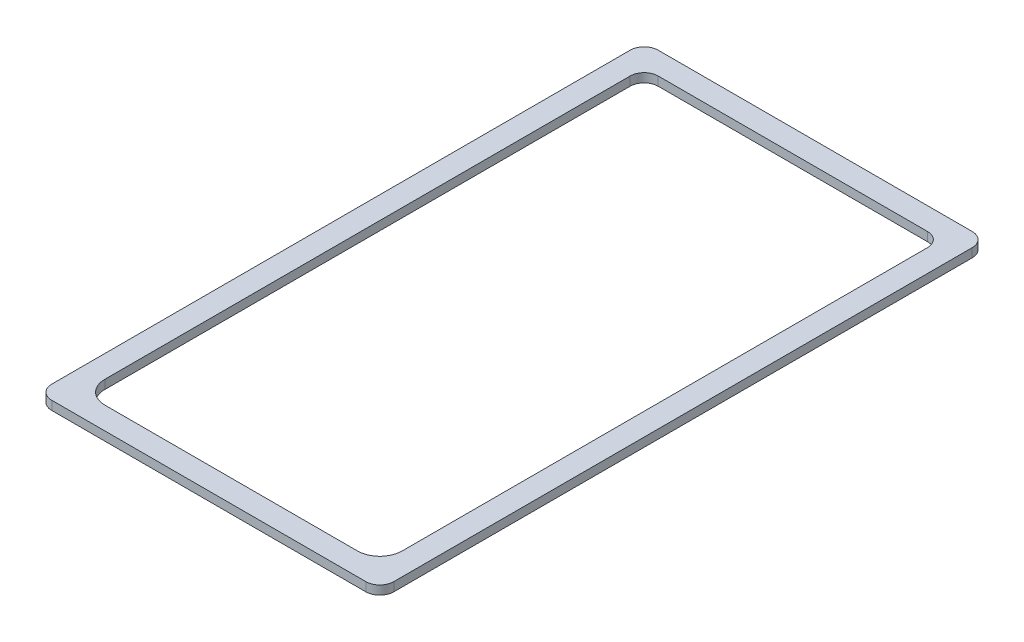
SolidWorks part; units mm, degrees
material "Rubber"
ref_plane "Front Plane" through (0, 0, 0) normal (0, 0, 1) x (1, 0, 0)
ref_plane "Top Plane" through (0, 0, 0) normal (0, 1, 0) x (1, 0, 0)
ref_plane "Right Plane" through (0, 0, 0) normal (1, 0, 0) x (0, 0, -1)
ref_axis "Axis1" through (0, 0, -88.99) along (0, 0, 1)
ref_axis "Axis2" through (0, -55, 0) along (0, 1, 0)
ref_axis "Axis3" through (-88.99, 0, 0) along (1, 0, 0)
sketch "Sketch1" plane through (0, 0, 0) normal (0, 1, 0) x (1, 0, 0)
  line L1 (28.1, -54.25) -> (-28.1, -54.25)
  line L2 (30.6, -51.75) -> (30.6, 51.75)
  line L3 (28.1, 54.25) -> (-28.1, 54.25)
  line L4 (-30.6, -51.75) -> (-30.6, 51.75)
  line L5 (30.6, -54.25) -> (-30.6, 54.25) construction
  line L6 (30.6, 54.25) -> (-30.6, -54.25) construction
  line L7 (22.6, -50.25) -> (-22.6, -50.25)
  line L8 (26.6, -46.25) -> (26.6, 47.75)
  line L9 (24.1, 50.25) -> (-24.1, 50.25)
  line L10 (-26.6, -46.25) -> (-26.6, 47.75)
  line L11 (26.6, -50.25) -> (-26.6, 50.25) construction
  line L12 (26.6, 50.25) -> (-26.6, -50.25) construction
  arc A0 (26.6, 47.75) -> (24.1, 50.25) centre (24.1, 47.75) ccw
  arc A1 (-24.1, 50.25) -> (-26.6, 47.75) centre (-24.1, 47.75) ccw
  arc A2 (22.6, -50.25) -> (26.6, -46.25) centre (22.6, -46.25) ccw
  arc A3 (-22.6, -50.25) -> (-26.6, -46.25) centre (-22.6, -46.25) cw
  arc A4 (28.1, -54.25) -> (30.6, -51.75) centre (28.1, -51.75) ccw
  arc A5 (-28.1, -54.25) -> (-30.6, -51.75) centre (-28.1, -51.75) cw
  arc A6 (30.6, 51.75) -> (28.1, 54.25) centre (28.1, 51.75) ccw
  arc A7 (-28.1, 54.25) -> (-30.6, 51.75) centre (-28.1, 51.75) ccw
  point P0 (0, 0)
  point P6 (0, 0)
  dimension "D5" = 2.5
  dimension "D6" = 4
  dimension "D7" = 2.5
  dimension "D8" = 2.5
  dimension "D1" = 108.5
  dimension "D2" = 4
  dimension "D3" = 61.2
  dimension "D4" = 4
extrude "Boss-Extrude1" add sketch "Sketch1" along normal blind 1.5875
